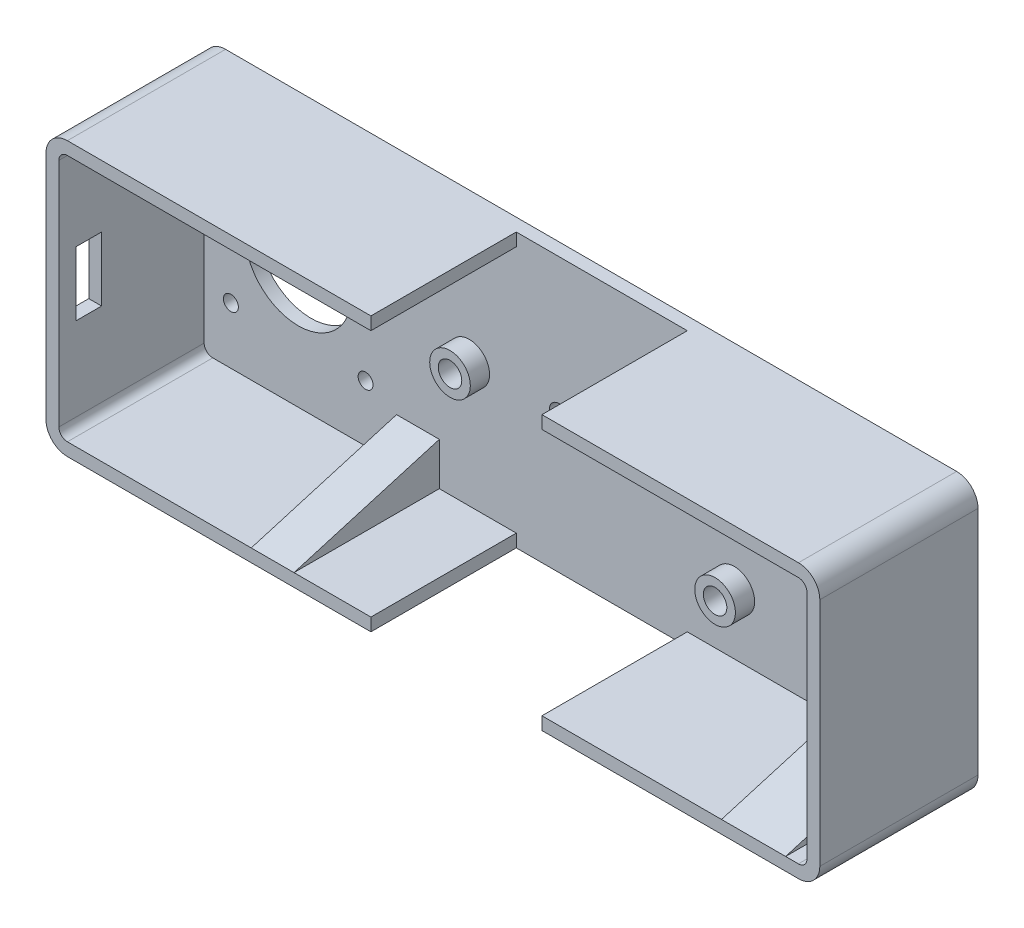
SolidWorks part; units mm, degrees
material "ABS"
ref_plane "Front Plane" through (0, 0, 0) normal (0, 0, 1) x (1, 0, 0)
ref_plane "Top Plane" through (0, 0, 0) normal (0, 1, 0) x (1, 0, 0)
ref_plane "Right Plane" through (0, 0, 0) normal (1, 0, 0) x (0, 0, -1)
sketch "Sketch1" plane through (0, 0, 0) normal (0, 0, 1) x (1, 0, 0)
  line L1 (-85.5, 32) -> (85.5, 32)
  line L2 (-90.5, 27) -> (-90.5, -27)
  line L3 (-85.5, -32) -> (85.5, -32)
  line L4 (90.5, 27) -> (90.5, -27)
  line L5 (-90.5, 32) -> (90.5, -32) construction
  line L6 (-90.5, -32) -> (90.5, 32) construction
  arc A0 (85.5, -32) -> (90.5, -27) centre (85.5, -27) ccw
  arc A1 (85.5, 32) -> (90.5, 27) centre (85.5, 27) cw
  arc A2 (-90.5, -27) -> (-85.5, -32) centre (-85.5, -27) ccw
  arc A3 (-85.5, 32) -> (-90.5, 27) centre (-85.5, 27) ccw
  point P0 (0, 0)
  dimension "D3" = 5
  dimension "D1" = 64
  dimension "D2" = 181
extrude "Boss-Extrude1" add sketch "Sketch1" along normal blind 37
sketch "Sketch2" plane through (0, 0, 37) normal (0, 0, 1) x (1, 0, 0)
  line L0 (-65.5, 0) -> (0, 0) construction
  line L1 (-49.75, 15.75) -> (-81.25, 15.75) construction
  line L2 (-49.75, 15.75) -> (-49.75, -15.75) construction
  line L3 (-49.75, -15.75) -> (-81.25, -15.75) construction
  line L4 (-81.25, 15.75) -> (-81.25, -15.75) construction
  line L5 (-49.75, 15.75) -> (-81.25, -15.75) construction
  line L6 (-49.75, -15.75) -> (-81.25, 15.75) construction
  line L7 (-90.5, 27) -> (-90.5, -27) construction
  line L8 (36.5, 15) -> (36.5, -15) construction
  line L9 (0, 0) -> (36.5, 0) construction
  line L10 (36.5, 0) -> (56.5, 0) construction
  circle A0 centre (-81.25, 15.75) radius 1.75
  circle A1 centre (-49.75, 15.75) radius 1.75
  circle A2 centre (-81.25, -15.75) radius 1.75
  circle A3 centre (-49.75, -15.75) radius 1.75
  circle A4 centre (-65.5, 0) radius 12.5
  circle A5 centre (36.5, 15) radius 2.75
  circle A6 centre (36.5, -15) radius 2.75
  circle A7 centre (-25.5, 0) radius 2.75
  circle A8 centre (56.5, 0) radius 2.25
  circle A9 centre (71.5, 0) radius 2.25
  point P0 (-65.5, 0)
  point P26 (0, 0)
  point P27 (69.1498, 0)
  dimension "D1" = 3.5
  dimension "D4" = 25
  dimension "D5" = 5.5
  dimension "D10" = 4.5
  dimension "D11" = 15
  dimension "D2" = 31.5
  dimension "D3" = 25
  dimension "D6" = 30
  dimension "D7" = 127
  dimension "D8" = 62
  dimension "D9" = 20
extrude "Cut-Extrude1" cut sketch "Sketch2" against normal through all
sketch "Sketch3" plane through (0, 0, 37) normal (0, 0, 1) x (1, 0, 0)
  circle A3 centre (36.5, 15) radius 2.75 construction
  circle A4 centre (36.5, 15) radius 2.75
  circle A5 centre (36.5, 15) radius 4.75
  circle A6 centre (-25.5, 0) radius 2.75 construction
  circle A7 centre (36.5, -15) radius 2.75 construction
  circle A8 centre (-25.5, 0) radius 2.75
  circle A9 centre (36.5, -15) radius 2.75
  circle A10 centre (-25.5, 0) radius 4.75
  circle A11 centre (36.5, -15) radius 4.75
  dimension "D1" = 2
  dimension "D2" = 2
sketch "Sketch4" plane through (0, 0, 0) normal (0, 0, 1) x (1, 0, 0)
  line L0 (90.5, 0) -> (90.5, -10) construction
  line L1 (90.5, -27) -> (90.5, 27) construction
  line L2 (0, 0) -> (90.5, 0) construction
  line L3 (90.5, 10) -> (100.5, 10) construction
  line L4 (90.5, -10) -> (100.5, -10) construction
  line L5 (100.5, 2.25) -> (100.5, -2.25) construction
  line L6 (100.5, 10) -> (100.5, 2.25) construction
  line L7 (100.5, -2.25) -> (100.5, -10) construction
  line L8 (90.5, 10) -> (90.5, 0) construction
  arc A0 (100.5, -10) -> (100.5, 10) centre (100.5, 0) ccw construction
  arc A1 (100.5, 2.25) -> (100.5, -2.25) centre (100.5, 0) ccw construction
  arc A2 (100.5, -2.25) -> (100.5, 2.25) centre (100.5, 0) ccw construction
  dimension "D3" = 4.5
  dimension "D1" = 20
  dimension "D2" = 10
sketch "Sketch5" plane through (0, 0, 37) normal (0, 0, 1) x (1, 0, 0)
  line L0 (-25.5, 0) -> (36.5, 0) construction
  line L1 (36.5, 0) -> (36.5, -15) construction
  circle A0 centre (-4.5, 0) radius 2.25
  circle A1 centre (15.5, 0) radius 2.25
  point P10 (5.5, 0)
  dimension "D3" = 4.5
  dimension "D1" = 10
  dimension "D2" = 10
extrude "Cut-Extrude2" cut sketch "Sketch5" against normal through all
sketch "Sketch6" plane through (0, 0, 37) normal (0, 0, 1) x (1, 0, 0)
  line L0 (85.5, 32) -> (-85.5, 32) construction
  line L1 (-85.5, -29) -> (85.5, -29)
  line L2 (-87.5, -27) -> (-87.5, 27)
  line L3 (-85.5, 29) -> (85.5, 29)
  line L4 (87.5, -27) -> (87.5, 27)
  line L5 (-87.5, -29) -> (87.5, 29) construction
  line L6 (-87.5, 29) -> (87.5, -29) construction
  line L7 (90.5, -27) -> (90.5, 27) construction
  arc A0 (-87.5, 27) -> (-85.5, 29) centre (-85.5, 27) cw
  arc A1 (-85.5, -29) -> (-87.5, -27) centre (-85.5, -27) cw
  arc A2 (85.5, -29) -> (87.5, -27) centre (85.5, -27) ccw
  arc A3 (85.5, 29) -> (87.5, 27) centre (85.5, 27) cw
  point P0 (0, 0)
  dimension "D3" = 2
  dimension "D1" = 3
  dimension "D2" = 3
extrude "Cut-Extrude3" cut sketch "Sketch6" against normal blind 34
sketch "Sketch7" plane through (0, 0, 3) normal (0, 0, 1) x (1, 0, 0)
  circle A0 centre (-25.5, 0) radius 4.75
  circle A1 centre (-25.5, 0) radius 2.75 construction
  circle A2 centre (36.5, -15) radius 4.75
  circle A3 centre (36.5, 15) radius 4.75
  circle A4 centre (36.5, -15) radius 2.75 construction
  dimension "D1" = 2
  dimension "D2" = 2
  dimension "D3" = 9.5
extrude "Boss-Extrude2" add sketch "Sketch7" along normal blind 4.5
sketch "Sketch10" plane through (0, 0, 37) normal (0, 0, 1) x (1, 0, 0)
  line L0 (-85.5, -32) -> (85.5, -32) construction
  line L1 (-14.5, -32) -> (25.5, -32)
  line L2 (-14.5, -32) -> (-14.5, 32)
  line L3 (-14.5, 32) -> (25.5, 32)
  line L4 (25.5, -32) -> (25.5, 32)
  line L5 (-14.5, -32) -> (25.5, 32) construction
  line L6 (-14.5, 32) -> (25.5, -32) construction
  line L7 (85.5, 32) -> (-85.5, 32) construction
  line L8 (5.5, 0) -> (36.5, 0) construction
  line L9 (0, 0) -> (90.5, 0) construction
  line L10 (36.5, 0) -> (36.5, -15) construction
  point P0 (5.5, 0)
  dimension "D1" = 40
  dimension "D2" = 31
extrude "Cut-Extrude4" cut sketch "Sketch10" against normal blind 34
sketch "Sketch11" plane through (0, 0, 7.5) normal (0, 0, 1) x (1, 0, 0)
  circle A0 centre (36.5, -15) radius 2.75
  circle A1 centre (-25.5, 0) radius 2.75
  circle A2 centre (36.5, 15) radius 2.75
  dimension "D1" = 5.5
  dimension "D2" = 5.5
  dimension "D3" = 5.5
extrude "Cut-Extrude5" cut sketch "Sketch11" against normal through all
sketch "Sketch12" plane through (0, 0, 3) normal (0, 0, 1) x (1, 0, 0)
  line L0 (25.5, -29) -> (85.5, -29) construction
  line L1 (67.5, -29) -> (82.5, -29)
  line L2 (67.5, -29) -> (67.5, -19)
  line L3 (67.5, -19) -> (82.5, -19)
  line L4 (82.5, -29) -> (82.5, -19)
  line L5 (90.5, 0) -> (32.1507, 0) construction
  line L6 (0, 0) -> (90.5, 0) construction
  line L7 (67.5, 19) -> (82.5, 19)
  line L8 (82.5, 29) -> (82.5, 19)
  line L9 (67.5, 29) -> (82.5, 29)
  line L10 (67.5, 29) -> (67.5, 19)
  line L11 (87.5, -27) -> (87.5, 27) construction
  line L12 (87.5, -6) -> (67.5, -6)
  line L13 (87.5, -6) -> (87.5, -16)
  line L14 (87.5, -16) -> (67.5, -16)
  line L15 (67.5, -6) -> (67.5, -16)
  line L16 (87.5, 16) -> (67.5, 16)
  line L17 (67.5, 6) -> (67.5, 16)
  line L18 (87.5, 6) -> (67.5, 6)
  line L19 (87.5, 6) -> (87.5, 16)
  line L20 (87.5, -27) -> (87.5, 27) construction
  line L21 (-85.5, -29) -> (-14.5, -29) construction
  line L22 (-42.5, -29) -> (-32.5, -29)
  line L23 (-42.5, -29) -> (-42.5, -19)
  line L24 (-42.5, -19) -> (-32.5, -19)
  line L25 (-32.5, -29) -> (-32.5, -19)
  line L26 (-42.5, 19) -> (-32.5, 19)
  line L27 (-32.5, 29) -> (-32.5, 19)
  line L28 (-42.5, 29) -> (-32.5, 29)
  line L29 (-42.5, 29) -> (-42.5, 19)
  line L30 (-87.5, 27) -> (-87.5, -27) construction
  dimension "D1" = 15
  dimension "D2" = 5
  dimension "D3" = 10
  dimension "D4" = 20
  dimension "D5" = 3
  dimension "D6" = 10
  dimension "D7" = 10
  dimension "D8" = 10
  dimension "D9" = 45
extrude "Boss-Extrude3" add sketch "Sketch12" along normal through all
sketch "Sketch14" plane through (0, -16, 0) normal (0, -1, 0) x (1, 0, 0)
  line L3 (87.5, 37) -> (67.5, 37)
  line L4 (67.5, 37) -> (67.5, 3)
  line L5 (67.5, 3) -> (87.5, 37)
  dimension "D1" = 34
extrude "Cut-Extrude6" cut sketch "Sketch14" against normal blind 33
sketch "Sketch16" plane through (82.5, 0, 0) normal (1, 0, 0) x (0, 0, -1)
  line L0 (-37, -19) -> (-3, -19)
  line L1 (-3, -19) -> (-37, -29)
  line L2 (-37, -27) -> (-37, 27) construction
  line L3 (-37, -29) -> (-37, -19)
  dimension "D1" = 10
  dimension "D2" = 34
extrude "Cut-Extrude8" cut sketch "Sketch16" against normal blind 15
sketch "Sketch17" plane through (67.5, 0, 0) normal (-1, 0, 0) x (0, 0, 1)
  line L6 (37, 19) -> (3, 19)
  line L7 (3, 19) -> (37, 29)
  line L8 (37, 29) -> (37, 19)
extrude "Cut-Extrude9" cut sketch "Sketch17" against normal blind 15
sketch "Sketch18" plane through (-32.5, 0, 0) normal (1, 0, 0) x (0, 0, -1)
  line L0 (-37, -29) -> (-37, -19)
  line L1 (-37, -19) -> (-3, -19)
  line L2 (-3, -19) -> (-37, -29)
extrude "Cut-Extrude10" cut sketch "Sketch18" against normal blind 10
sketch "Sketch19" plane through (-32.5, 0, 0) normal (1, 0, 0) x (0, 0, -1)
  line L0 (-37, 29) -> (-3, 19)
  line L1 (-3, 19) -> (-37, 19)
  line L2 (-37, 19) -> (-37, 29)
extrude "Cut-Extrude11" cut sketch "Sketch19" against normal blind 10
sketch "Sketch20" plane through (-90.5, 0, 0) normal (-1, 0, 0) x (0, 0, 1)
  line L0 (37, 27) -> (37, -27) construction
  line L1 (33, 7.5) -> (27, 7.5)
  line L2 (33, 7.5) -> (33, -7.5)
  line L3 (33, -7.5) -> (27, -7.5)
  line L4 (27, 7.5) -> (27, -7.5)
  line L5 (33, 7.5) -> (27, -7.5) construction
  line L6 (33, -7.5) -> (27, 7.5) construction
  line L7 (0, 0) -> (37, 0) construction
  line L8 (37, -2.75) -> (37, 2.75) construction
  point P0 (30, 0)
  dimension "D1" = 4
  dimension "D2" = 15
  dimension "D3" = 6
extrude "Cut-Extrude12" cut sketch "Sketch20" against normal blind 3
